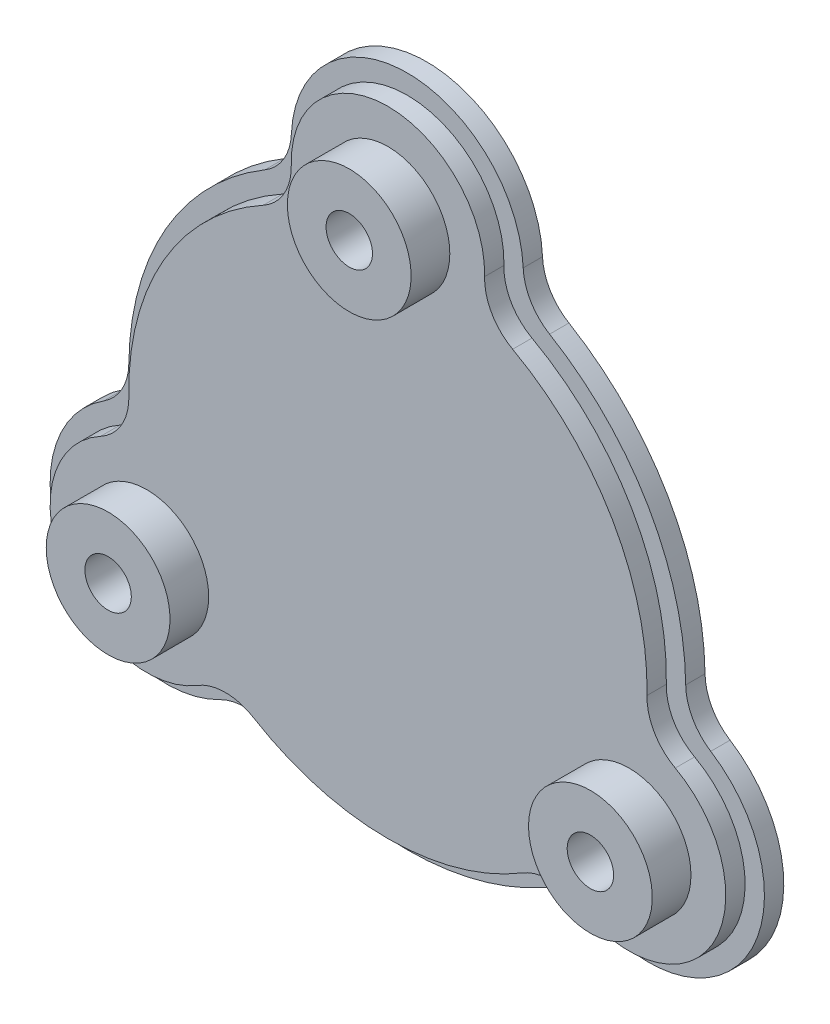
SolidWorks part; units mm, degrees
material "PE Low/Medium Density"
ref_plane "Front Plane" through (0, 0, 0) normal (0, 0, 1) x (1, 0, 0)
ref_plane "Top Plane" through (0, 0, 0) normal (0, 1, 0) x (1, 0, 0)
ref_plane "Right Plane" through (0, 0, 0) normal (1, 0, 0) x (0, 0, -1)
sketch "Sketch1" plane through (0, 0, 0) normal (0, 0, 1) x (1, 0, 0)
  arc A0 (-21.1352, -29.1428) -> (21.1352, -29.1428) centre (0, 0) ccw
  arc A1 (14.6709, 32.875) -> (-14.6709, 32.875) centre (0, 36) ccw
  arc A2 (21.1352, -29.1428) -> (35.806, -3.7322) centre (31.1769, -18) ccw
  arc A3 (-21.1352, -29.1428) -> (21.1352, -29.1428) centre (0, 0) ccw
  arc A4 (-35.806, -3.7322) -> (-21.1352, -29.1428) centre (-31.1769, -18) ccw
  arc A5 (-21.1352, -29.1428) -> (21.1352, -29.1428) centre (0, 0) ccw
  arc A6 (35.806, -3.7322) -> (14.6709, 32.875) centre (0, 0) ccw
  arc A7 (35.806, -3.7322) -> (14.6709, 32.875) centre (0, 0) ccw
  arc A8 (35.806, -3.7322) -> (14.6709, 32.875) centre (0, 0) ccw
  arc A9 (-14.6709, 32.875) -> (-35.806, -3.7322) centre (0, 0) ccw
  arc A10 (-14.6709, 32.875) -> (-35.806, -3.7322) centre (0, 0) ccw
  arc A11 (-14.6709, 32.875) -> (-35.806, -3.7322) centre (0, 0) ccw
  circle A12 centre (0, 36) radius 5.5
  circle A13 centre (-31.1769, -18) radius 3
  circle A14 centre (31.1769, -18) radius 5.5
  arc A15 (-11.6294, 31.4167) -> (-33.0223, -5.637) centre (0, 0) ccw
  arc A16 (-33.0223, -5.637) -> (-21.3929, -25.7797) centre (-31.1769, -18) ccw
  arc A17 (-21.3929, -25.7797) -> (21.3929, -25.7797) centre (0, 0) ccw
  arc A18 (21.3929, -25.7797) -> (33.0223, -5.637) centre (31.1769, -18) ccw
  arc A19 (33.0223, -5.637) -> (11.6294, 31.4167) centre (0, 0) ccw
  arc A20 (11.6294, 31.4167) -> (-11.6294, 31.4167) centre (0, 36) ccw
  circle A21 centre (-31.1769, -18) radius 5.5
  circle A22 centre (0, 36) radius 3
  circle A23 centre (31.1769, -18) radius 3
  point P14 (0, 0)
  dimension "D1" = 72
  dimension "D3" = 30
  dimension "D5" = 11
  dimension "D6" = 6
  dimension "D7" = 11
  dimension "D9" = 11
  dimension "D10" = 6
  dimension "D11" = 6
  dimension "D2" = 36
  dimension "D8" = 2.5
  dimension "D4" = 3
extrude "Boss-Extrude3" add sketch "Sketch1" along normal blind 2.5 contours A1 A9 A4 A0 A2 A6 A20 A19 A18 A17 A16 A15 | A19 A20 A15 A16 A17 A18 A21 A12 A14 region at (-43.0685, -24.8656, 0) region at (0, 0, 0)
extrude "Boss-Extrude4" add sketch "Sketch1<7>" along normal blind 5 contours A19 A20 A15 A16 A17 A18 A21 A12 A14 region at (0, 0, 0)
sketch "Sketch1<7>" plane through (0, 0, 0) normal (0, 0, 1) x (1, 0, 0) same geometry as "Sketch1"
sketch "Sketch2" plane through (0, 0, 0) normal (0, 0, -1) x (-1, 0, 0)
  circle A10 centre (0, 36) radius 8
  circle A11 centre (-31.1769, -18) radius 5.5 construction
  circle A12 centre (-31.1769, -18) radius 8
  circle A13 centre (31.1769, -18) radius 8
  point P4 (-86.2577, -4.4449)
  point P5 (0, 0)
  dimension "D2" = 16
  dimension "D3" = 16
  dimension "D1" = 16
extrude "Boss-Extrude5" add sketch "Sketch2" against normal blind 10
extrude "Cut-Extrude2" cut sketch "Sketch1<9>" along normal through all contours A22 | A23 | A13 region at (-31.1769, -18, 0) region at (0, 36, 0) region at (31.1769, -18, 0)
sketch "Sketch1<9>" plane through (0, 0, 0) normal (0, 0, 1) x (1, 0, 0) same geometry as "Sketch1"
extrude "Cut-Extrude3" cut sketch "Sketch1<13>" along normal blind 5 contours A12 A22 | A14 A23 | A21 A13 region at (-5.3444, 36, 0) region at (25.8325, -18, 0) region at (-36.5214, -18, 0)
sketch "Sketch1<13>" plane through (0, 0, 0) normal (0, 0, 1) x (1, 0, 0) same geometry as "Sketch1"
fillet "Fillet1" radius 7 12 edges at (35.806, -3.7322, 1.25) (21.1352, -29.1428, 1.25) (-21.1352, -29.1428, 1.25) (-35.806, -3.7322, 1.25) (-14.6709, 32.875, 1.25) (14.6709, 32.875, 1.25) (33.0223, -5.637, 3.75) (21.3929, -25.7797, 3.75) (-21.3929, -25.7797, 3.75) (-33.0223, -5.637, 3.75) (-11.6294, 31.4167, 3.75) (11.6294, 31.4167, 3.75)
equation "\"A\" = 36"
equation "\"B\" = 10"
equation "\"C\" = 2.5"
equation "\"D1@Sketch1\"=\"A\"*2"
equation "\"D8@Sketch1\"=\"C\""
equation "\"D1@Boss-Extrude3\"=\"C\""
equation "\"D1@Boss-Extrude4\"=\"C\"*2"
equation "\"D1@Boss-Extrude5\"=\"B\""
equation "\"D1@Cut-Extrude3\"=\"B\"-(\"C\"*2)"
